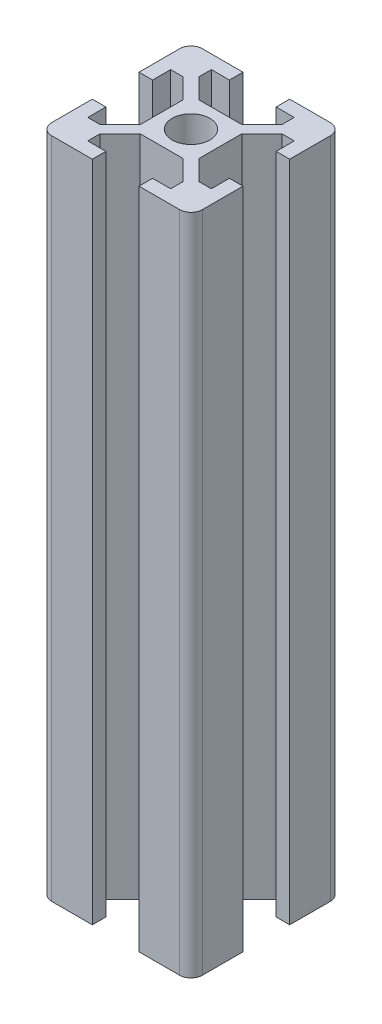
SolidWorks part; units mm, degrees
ref_plane "Płaszczyzna przednia" through (0, 0, 0) normal (0, 0, 1) x (1, 0, 0)
ref_plane "Płaszczyzna górna" through (0, 0, 0) normal (0, 1, 0) x (1, 0, 0)
ref_plane "Płaszczyzna prawa" through (0, 0, 0) normal (1, 0, 0) x (0, 0, -1)
sketch "Szkic1" plane through (0, 0, 0) normal (0, 1, 0) x (1, 0, 0)
  line L0 (0, 10) -> (0, -10) construction
  line L1 (-10, 0) -> (10, 0) construction
  line L2 (0, 3.9) -> (2.8393, 3.9)
  line L3 (3.9, 2.8393) -> (3.9, 0)
  line L4 (10, 3.1) -> (10, 8.5)
  line L5 (8.5, 10) -> (3.1, 10)
  line L6 (3.1, 10) -> (3.1, 8.2)
  line L7 (3.1, 8.2) -> (5.5, 8.2)
  line L8 (5.5, 8.2) -> (5.5, 6.5607)
  line L9 (5.5, 6.5607) -> (2.8393, 3.9)
  line L10 (3.9, 2.8393) -> (6.5607, 5.5)
  line L11 (6.5607, 5.5) -> (8.2, 5.5)
  line L12 (8.2, 5.5) -> (8.2, 3.1)
  line L13 (8.2, 3.1) -> (10, 3.1)
  line L14 (3.9, 0) -> (3.9, -2.8393)
  line L15 (2.8393, -3.9) -> (0, -3.9)
  line L16 (3.1, -10) -> (8.5, -10)
  line L17 (10, -8.5) -> (10, -3.1)
  line L18 (10, -3.1) -> (8.2, -3.1)
  line L19 (8.2, -3.1) -> (8.2, -5.5)
  line L20 (8.2, -5.5) -> (6.5607, -5.5)
  line L21 (6.5607, -5.5) -> (3.9, -2.8393)
  line L22 (2.8393, -3.9) -> (5.5, -6.5607)
  line L23 (5.5, -6.5607) -> (5.5, -8.2)
  line L24 (5.5, -8.2) -> (3.1, -8.2)
  line L25 (3.1, -8.2) -> (3.1, -10)
  line L26 (10, 0) -> (-10, 0) construction
  line L27 (0, 10) -> (0, -10) construction
  line L28 (0, -3.9) -> (-2.8393, -3.9)
  line L29 (-3.9, -2.8393) -> (-3.9, 0)
  line L30 (-10, -3.1) -> (-10, -8.5)
  line L31 (-8.5, -10) -> (-3.1, -10)
  line L32 (-3.1, -10) -> (-3.1, -8.2)
  line L33 (-3.1, -8.2) -> (-5.5, -8.2)
  line L34 (-5.5, -8.2) -> (-5.5, -6.5607)
  line L35 (-5.5, -6.5607) -> (-2.8393, -3.9)
  line L36 (-3.9, -2.8393) -> (-6.5607, -5.5)
  line L37 (-6.5607, -5.5) -> (-8.2, -5.5)
  line L38 (-8.2, -5.5) -> (-8.2, -3.1)
  line L39 (-8.2, -3.1) -> (-10, -3.1)
  line L40 (0, -10) -> (0, 10) construction
  line L41 (10, 0) -> (-10, 0) construction
  line L42 (-3.9, 0) -> (-3.9, 2.8393)
  line L43 (-2.8393, 3.9) -> (0, 3.9)
  line L44 (-3.1, 10) -> (-8.5, 10)
  line L45 (-10, 8.5) -> (-10, 3.1)
  line L46 (-10, 3.1) -> (-8.2, 3.1)
  line L47 (-8.2, 3.1) -> (-8.2, 5.5)
  line L48 (-8.2, 5.5) -> (-6.5607, 5.5)
  line L49 (-6.5607, 5.5) -> (-3.9, 2.8393)
  line L50 (-2.8393, 3.9) -> (-5.5, 6.5607)
  line L51 (-5.5, 6.5607) -> (-5.5, 8.2)
  line L52 (-5.5, 8.2) -> (-3.1, 8.2)
  line L53 (-3.1, 8.2) -> (-3.1, 10)
  line L54 (-10, 0) -> (10, 0) construction
  line L55 (0, -10) -> (0, 10) construction
  arc A0 (2.5, 0) -> (0, 2.5) centre (0, 0) ccw
  arc A1 (10, 8.5) -> (8.5, 10) centre (8.5, 8.5) ccw
  arc A2 (0, -2.5) -> (2.5, 0) centre (0, 0) ccw
  arc A3 (8.5, -10) -> (10, -8.5) centre (8.5, -8.5) ccw
  arc A4 (-2.5, 0) -> (0, -2.5) centre (0, 0) ccw
  arc A5 (-10, -8.5) -> (-8.5, -10) centre (-8.5, -8.5) ccw
  arc A6 (0, 2.5) -> (-2.5, 0) centre (0, 0) ccw
  arc A7 (-8.5, 10) -> (-10, 8.5) centre (-8.5, 8.5) ccw
  point P6 (0, 0)
  point P90 (0, 0)
  dimension "D2" = 45
  dimension "D3" = 2.5
  dimension "D7" = 1.5
  dimension "D1" = 20
  dimension "D4" = 6.1
  dimension "D5" = 11
  dimension "D6" = 6.2
  dimension "D8" = 1.8
  dimension "D9" = 1.5
  dimension "D10" = 4
extrude "Dodanie-wyciągnięcie1" add sketch "Szkic1" along normal blind 88 contours L44 A7 L45 L46 L47 L48 L49 L42 L29 L36 L37 L38 L39 L30 A5 L31 L32 L33 L34 L35 L28 L15 L22 L23 L24 L25 L16 A3 L17 L18 L19 L20 L21 L14 L3 L10 L11 L12 L13 L4 A1 L5 L6 L7 L8 L9 L2 L43 L50 L51 L52 region at (1.4197, 0, -3.6172)
